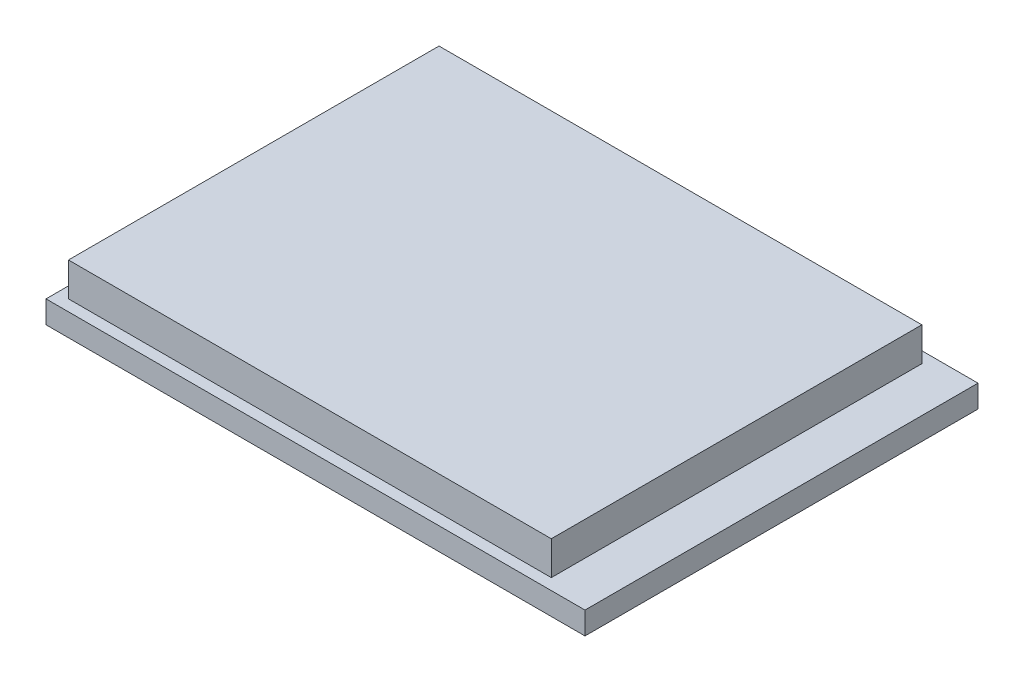
SolidWorks part; units mm, degrees
ref_plane "Front Plane" through (0, 0, 0) normal (0, 0, 1) x (1, 0, 0)
ref_plane "Top Plane" through (0, 0, 0) normal (0, 1, 0) x (1, 0, 0)
ref_plane "Right Plane" through (0, 0, 0) normal (1, 0, 0) x (0, 0, -1)
sketch "Sketch1" plane through (0, 0, 0) normal (0, 1, 0) x (1, 0, 0)
  line L1 (0, 0) -> (48, 0)
  line L2 (0, 0) -> (0, -35)
  line L3 (0, -35) -> (48, -35)
  line L4 (48, 0) -> (48, -35)
  dimension "D1" = 48
  dimension "D2" = 35
extrude "Boss-Extrude1" add sketch "Sketch1" along normal blind 2
sketch "Sketch2" plane through (0, 2, 0) normal (0, 1, 0) x (1, 0, 0)
  line L0 (48, 0) -> (0, 0) construction
  line L1 (1, -1) -> (44, -1)
  line L2 (1, -1) -> (1, -34)
  line L3 (1, -34) -> (44, -34)
  line L4 (44, -1) -> (44, -34)
  line L5 (0, 0) -> (0, -35) construction
  dimension "D1" = 43
  dimension "D2" = 33
  dimension "D3" = 1
  dimension "D4" = 1
extrude "Boss-Extrude2" add sketch "Sketch2" along normal blind 3
sketch "Sketch3" plane through (0, 0, 0) normal (0, -1, 0) x (1, 0, 0)
  line L0 (0, 35) -> (48, 35) construction
  line L1 (25.0892, 20) -> (30.5804, 20)
  line L2 (25.0892, 20) -> (25.0892, 17)
  line L3 (25.0892, 17) -> (30.5804, 17)
  line L4 (30.5804, 20) -> (30.5804, 17)
  dimension "D1" = 15
  dimension "D2" = 3
extrude "Boss-Extrude3" add sketch "Sketch3" along normal blind 5
sketch "Sketch4" plane through (0, 0, 20) normal (0, 0, 1) x (1, 0, 0)
  circle A0 centre (27.5602, -2.6198) radius 1
  dimension "D1" = 2
extrude "Cut-Extrude1" cut sketch "Sketch4" against normal through all
